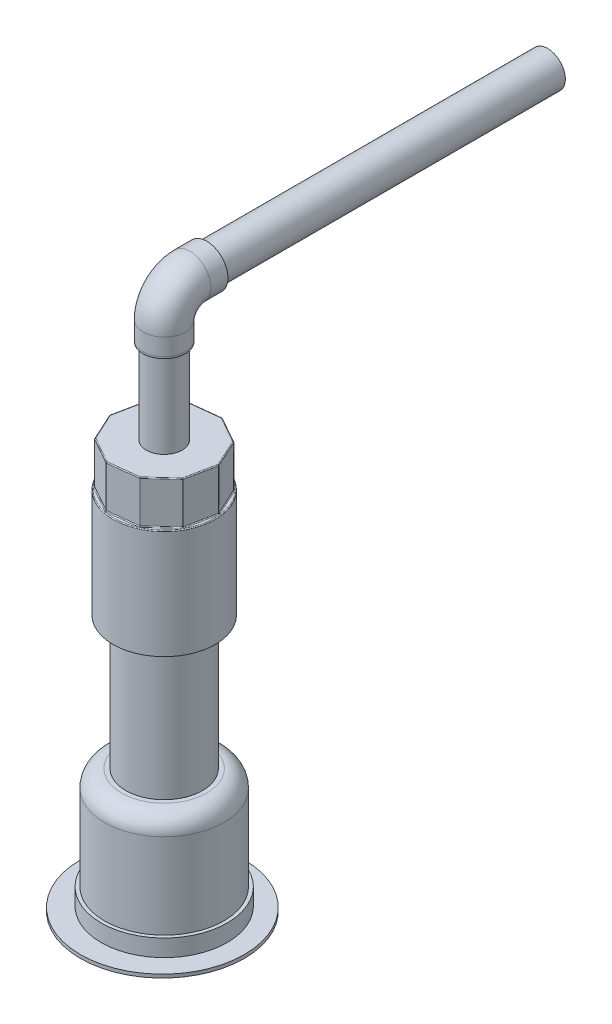
SolidWorks part; units mm, degrees
ref_plane "Front Plane" through (0, 0, 0) normal (0, 0, 1) x (1, 0, 0)
ref_plane "Top Plane" through (0, 0, 0) normal (0, 1, 0) x (1, 0, 0)
ref_plane "Right Plane" through (0, 0, 0) normal (1, 0, 0) x (0, 0, -1)
sketch "Sketch3" plane through (0, 0, 0) normal (0, 1, 0) x (1, 0, 0)
  circle A0 centre (0, -1.0667) radius 48.1
  dimension "D1" = 96.2
extrude "Boss-Extrude3" add sketch "Sketch3" along normal blind 200 contours A0
sketch "Sketch4" plane through (0, 200, 0) normal (0, 1, 0) x (1, 0, 0)
  circle A0 centre (0, 0) radius 35
  circle M2 centre (0, -1.0667) radius 48.1
  dimension "D1" = 70
extrude "Cut-Extrude2" cut sketch "Sketch4" against normal blind 198 contours A0 M2 region at (-46.7395, 200, 1.0667)
sketch "Sketch5" plane through (0, 200, 0) normal (0, 1, 0) x (1, 0, 0)
  circle A0 centre (0, 0) radius 22.5
  circle M2 centre (0, 0) radius 35
  dimension "D1" = 45
extrude "Cut-Extrude3" cut sketch "Sketch5" against normal blind 128 contours A0 M2 region at (-34.0101, 200, 0)
fillet "Fillet1" radius 10 1 edges at (0, 72, 35) type face fillet first side face at (0, 72, 22.5) second side face at (0, 2, 35)
ref_plane "Plane2" through (0, 150, 0) normal (0, 1, 0) x (1, 0, 0)
sketch "Sketch6" plane through (0, 200, 0) normal (0, 1, 0) x (1, 0, 0)
  circle A0 centre (0, 0) radius 20.5
  circle A1 centre (0, 0) radius 22.5 construction
  dimension "D1" = 2
extrude "Cut-Extrude4" cut sketch "Sketch6" against normal up to vertex (200 mm away) up to point (0, 0, 0)
fillet "Fillet2" radius 2 1 edges at (0, 2, 35) type face fillet first side face at (0, 2, 35) second side face at (0, 62, 35)
sketch "Sketch7" plane through (0, 0, 0) normal (0, -1, 0) x (-1, 0, 0)
  circle A0 centre (0, 0) radius 34.5
  dimension "D1" = 69
extrude "Cut-Extrude9" cut sketch "Sketch7" against normal blind 56
fillet "Fillet3" radius 4 1 edges at (0, 56, -34.5) type face fillet first side face at (0, 56, -34.5) second side face at (0, 56, -34.5)
sketch "Sketch8" plane through (0, 56, 0) normal (0, -1, 0) x (1, 0, 0)
  line L0 (-12.8244, 15.9933) -> (-10.2294, 12.757)
  line L1 (2.2407, 20.3772) -> (1.7873, 16.2539)
  line L2 (15.9933, 12.8244) -> (12.757, 10.2294)
  line L3 (20.3772, -2.2407) -> (16.2539, -1.7873)
  line L4 (12.8244, -15.9933) -> (10.2294, -12.757)
  line L5 (-2.2407, -20.3772) -> (-1.7873, -16.2539)
  line L6 (-15.9933, -12.8244) -> (-12.757, -10.2294)
  line L7 (-20.3772, 2.2407) -> (-16.2539, 1.7873)
  line L8 (-14.3847, 14.7421) -> (-11.7897, 11.5059)
  line L9 (-20.5958, 0.2527) -> (-16.4725, -0.2007)
  line L10 (-14.7421, -14.3847) -> (-11.5059, -11.7897)
  line L11 (-0.2527, -20.5958) -> (0.2007, -16.4725)
  line L12 (14.3847, -14.7421) -> (11.7897, -11.5059)
  line L13 (20.5958, -0.2527) -> (16.4725, 0.2007)
  line L14 (14.7421, 14.3847) -> (11.5059, 11.7897)
  line L15 (0.2527, 20.5958) -> (-0.2007, 16.4725)
  line L16 (1.4401, 6.4909) -> (3.1298, 7.561)
  line L17 (-3.1333, 7.5595) -> (-3.5715, 5.6081)
  line L18 (-7.561, 3.1298) -> (-6.4909, 1.4401)
  line L19 (7.5595, 3.1333) -> (5.6081, 3.5715)
  line L20 (6.4909, -1.4401) -> (7.561, -3.1298)
  line L21 (3.5715, -5.6081) -> (3.1333, -7.5595)
  line L22 (-1.4401, -6.4909) -> (-3.1298, -7.561)
  line L23 (-5.6081, -3.5715) -> (-7.5595, -3.1333)
  line L24 (2.2407, 20.3772) -> (0.2527, 20.5958)
  line L25 (14.7421, 14.3847) -> (15.9933, 12.8244)
  line L26 (20.5958, -0.2527) -> (20.3772, -2.2407)
  line L27 (14.3847, -14.7421) -> (12.8244, -15.9933)
  line L28 (-0.2527, -20.5958) -> (-2.2407, -20.3772)
  line L29 (-14.7421, -14.3847) -> (-15.9933, -12.8244)
  line L30 (-20.5958, 0.2527) -> (-20.3772, 2.2407)
  line L31 (-12.8244, 15.9933) -> (-14.3847, 14.7421)
  circle A0 centre (0, 0) radius 8.1831
  circle A1 centre (0, 0) radius 10.8912
  circle A2 centre (0, 0) radius 13.5226
  circle A3 centre (0, 0) radius 16.3519
  circle A4 centre (0, 0) radius 20.5
  arc A5 (-10.2294, 12.757) -> (-9.222, 9.8903) centre (-13.8046, 9.8903) cw
  arc A6 (-9.222, 9.8903) -> (-7.3599, 8.0282) centre (-7.3599, 9.8903) ccw
  arc A7 (-7.3599, 8.0282) -> (-3.1333, 7.5595) centre (-7.3599, -11.2637) cw
  arc A8 (0.4725, 10.881) -> (3.1298, 7.561) centre (-13.1689, -2.7605) cw
  arc A9 (0.4725, 13.5144) -> (0.4725, 10.881) centre (1.7893, 12.1977) ccw
  arc A10 (1.7873, 16.2539) -> (0.4725, 13.5144) centre (-2.7678, 16.7548) cw
  arc A11 (8.0282, 7.3599) -> (7.5595, 3.1333) centre (-11.2637, 7.3599) cw
  arc A12 (9.8903, 9.222) -> (8.0282, 7.3599) centre (9.8903, 7.3599) ccw
  arc A13 (12.757, 10.2294) -> (9.8903, 9.222) centre (9.8903, 13.8046) cw
  arc A14 (10.881, -0.4725) -> (7.561, -3.1298) centre (-2.7605, 13.1689) cw
  arc A15 (13.5144, -0.4725) -> (10.881, -0.4725) centre (12.1977, -1.7893) ccw
  arc A16 (16.2539, -1.7873) -> (13.5144, -0.4725) centre (16.7548, 2.7678) cw
  arc A17 (7.3599, -8.0282) -> (3.1333, -7.5595) centre (7.3599, 11.2637) cw
  arc A18 (9.222, -9.8903) -> (7.3599, -8.0282) centre (7.3599, -9.8903) ccw
  arc A19 (10.2294, -12.757) -> (9.222, -9.8903) centre (13.8046, -9.8903) cw
  arc A20 (-0.4725, -10.881) -> (-3.1298, -7.561) centre (13.1689, 2.7605) cw
  arc A21 (-0.4725, -13.5144) -> (-0.4725, -10.881) centre (-1.7893, -12.1977) ccw
  arc A22 (-1.7873, -16.2539) -> (-0.4725, -13.5144) centre (2.7678, -16.7548) cw
  arc A23 (-8.0282, -7.3599) -> (-7.5595, -3.1333) centre (11.2637, -7.3599) cw
  arc A24 (-9.8903, -9.222) -> (-8.0282, -7.3599) centre (-9.8903, -7.3599) ccw
  arc A25 (-12.757, -10.2294) -> (-9.8903, -9.222) centre (-9.8903, -13.8046) cw
  arc A26 (-10.881, 0.4725) -> (-7.561, 3.1298) centre (2.7605, -13.1689) cw
  arc A27 (-13.5144, 0.4725) -> (-10.881, 0.4725) centre (-12.1977, 1.7893) ccw
  arc A28 (-16.2539, 1.7873) -> (-13.5144, 0.4725) centre (-16.7548, -2.7678) cw
  arc A29 (-11.7897, 11.5059) -> (-11.222, 9.8903) centre (-13.8046, 9.8903) cw
  arc A30 (-11.222, 9.8903) -> (-7.3599, 6.0282) centre (-7.3599, 9.8903) ccw
  arc A31 (-7.3599, 6.0282) -> (-3.5715, 5.6081) centre (-7.3599, -11.2637) cw
  arc A32 (-16.4725, -0.2007) -> (-14.9286, -0.9417) centre (-16.7548, -2.7678) cw
  arc A33 (-14.9286, -0.9417) -> (-9.4668, -0.9417) centre (-12.1977, 1.7893) ccw
  arc A34 (-9.4668, -0.9417) -> (-6.4909, 1.4401) centre (2.7605, -13.1689) cw
  arc A35 (-11.5059, -11.7897) -> (-9.8903, -11.222) centre (-9.8903, -13.8046) cw
  arc A36 (-9.8903, -11.222) -> (-6.0282, -7.3599) centre (-9.8903, -7.3599) ccw
  arc A37 (-6.0282, -7.3599) -> (-5.6081, -3.5715) centre (11.2637, -7.3599) cw
  arc A38 (0.2007, -16.4725) -> (0.9417, -14.9286) centre (2.7678, -16.7548) cw
  arc A39 (0.9417, -14.9286) -> (0.9417, -9.4668) centre (-1.7893, -12.1977) ccw
  arc A40 (0.9417, -9.4668) -> (-1.4401, -6.4909) centre (13.1689, 2.7605) cw
  arc A41 (11.7897, -11.5059) -> (11.222, -9.8903) centre (13.8046, -9.8903) cw
  arc A42 (11.222, -9.8903) -> (7.3599, -6.0282) centre (7.3599, -9.8903) ccw
  arc A43 (7.3599, -6.0282) -> (3.5715, -5.6081) centre (7.3599, 11.2637) cw
  arc A44 (16.4725, 0.2007) -> (14.9286, 0.9417) centre (16.7548, 2.7678) cw
  arc A45 (14.9286, 0.9417) -> (9.4668, 0.9417) centre (12.1977, -1.7893) ccw
  arc A46 (9.4668, 0.9417) -> (6.4909, -1.4401) centre (-2.7605, 13.1689) cw
  arc A47 (11.5059, 11.7897) -> (9.8903, 11.222) centre (9.8903, 13.8046) cw
  arc A48 (9.8903, 11.222) -> (6.0282, 7.3599) centre (9.8903, 7.3599) ccw
  arc A49 (6.0282, 7.3599) -> (5.6081, 3.5715) centre (-11.2637, 7.3599) cw
  arc A50 (-0.2007, 16.4725) -> (-0.9417, 14.9286) centre (-2.7678, 16.7548) cw
  arc A51 (-0.9417, 14.9286) -> (-0.9417, 9.4668) centre (1.7893, 12.1977) ccw
  arc A52 (-0.9417, 9.4668) -> (1.4401, 6.4909) centre (-13.1689, -2.7605) cw
  point P135 (0, 0)
  dimension "D2" = 2
  dimension "D1" = 8
extrude "Boss-Extrude15" add sketch "Sketch8" against normal blind 3 contours A52 A0 L17 A31 L18 A34 L23 A37 L22 A40 L21 A43 L20 A46 L19 A49 L16 | L5 A22 A21 A20 L22 A40 A39 A38 L11 L28 | L4 A19 A18 A17 L21 A43 A42 A41 L12 L27 | A15 A14 L20 A46 A45 A44 L13 L26 L3 A16 | A48 A49 L19 A11 A12 A13 L2 L25 L14 A47 | A52 L16 A8 A9 A10 L1 L24 L15 A50 A51 | A30 A31 L17 A7 A6 A5 L0 L31 L8 A29 | L9 A32 A33 A34 L18 A26 A27 A28 L7 L30 | L6 A25 A24 A23 L23 A37 A36 A35 L10 L29 region at (0, 56, 0)
sketch "Sketch9" plane through (0, 56, 0) normal (0, -1, 0) x (1, 0, 0)
  circle A0 centre (0, 0) radius 16.6577
  circle A1 centre (0, 0) radius 13.5859
extrude "Boss-Extrude16" add sketch "Sketch9" against normal blind 3
sketch "Sketch10" plane through (0, 150, 0) normal (0, 1, 0) x (1, 0, 0)
  circle A0 centre (0, 0) radius 30
  circle A1 centre (0, 0) radius 25 construction
  dimension "D1" = 5
extrude "Boss-Extrude17" add sketch "Sketch10" along normal blind 89
sketch "Sketch11" plane through (0, 239, 0) normal (0, 1, 0) x (1, 0, 0)
  circle A0 centre (0, 0) radius 10.5
  dimension "D1" = 21
extrude "Cut-Extrude10" cut sketch "Sketch11" against normal blind 89
sketch "Sketch12" plane through (0, 239, 0) normal (0, 1, 0) x (1, 0, 0)
  circle A0 centre (0, 0) radius 23
  circle A1 centre (0, 0) radius 30 construction
  circle M3 centre (0, 0) radius 30
  dimension "D1" = 7
extrude "Cut-Extrude12" cut sketch "Sketch12" against normal blind 25 contours A0 M3 region at (-29.1515, 239, 0)
sketch "Sketch13" plane through (0, 239, 0) normal (0, 1, 0) x (1, 0, 0)
  line L1 (21.2917, 19.564) -> (5.7259, 28.3426)
  line L2 (5.7259, 28.3426) -> (-12.027, 26.2953)
  line L3 (-12.027, 26.2953) -> (-25.186, 14.204)
  line L4 (-25.186, 14.204) -> (-28.7248, -3.3127)
  line L5 (-28.7248, -3.3127) -> (-21.2917, -19.564)
  line L6 (-21.2917, -19.564) -> (-5.7259, -28.3426)
  line L7 (-5.7259, -28.3426) -> (12.027, -26.2953)
  line L8 (12.027, -26.2953) -> (25.186, -14.204)
  line L9 (25.186, -14.204) -> (28.7248, 3.3127)
  line L10 (28.7248, 3.3127) -> (21.2917, 19.564)
  circle A0 centre (0, 0) radius 27.5 construction
  circle A2 centre (0, 0) radius 23 construction
  circle M11 centre (0, 0) radius 10.5
  circle M12 centre (0, 0) radius 23
  dimension "D1" = 27.5
extrude "Boss-Extrude18" add sketch "Sketch13" against normal up to surface (25 mm away) contours M12 M11 | L1 L2 L3 L4 L5 L6 L7 L8 L9 L10 region at (-22.3495, 239, 0) up to face at (0, 214, 23)
fillet "Fillet4" radius 0.5 31 edges at (0, 214, 30) (-13.5088, 239, 23.9533) (-13.5088, 214, 23.9533) (-25.0083, 239, 11.4384) (-21.2917, 226.5, 19.564) (-25.0083, 214, 11.4384) (-26.9554, 239, -5.4457) (-28.7248, 226.5, 3.3127) (-26.9554, 214, -5.4457) (-18.6065, 239, -20.2496) (-25.186, 226.5, -14.204) (-18.6065, 214, -20.2496) (-3.1505, 239, -27.3189) (-12.027, 226.5, -26.2953) (-3.1505, 214, -27.3189) (13.5088, 239, -23.9533) (5.7259, 226.5, -28.3426) (13.5088, 214, -23.9533) (25.0083, 239, -11.4384) (21.2917, 226.5, -19.564) (25.0083, 214, -11.4384) (26.9554, 239, 5.4457) (28.7248, 226.5, -3.3127) (26.9554, 214, 5.4457) (-5.7259, 226.5, 28.3426) (3.1505, 239, 27.3189) (3.1505, 214, 27.3189) (12.027, 226.5, 26.2953) (18.6065, 239, 20.2496) (25.186, 226.5, 14.204) (18.6065, 214, 20.2496)
sketch "Sketch14" plane through (0, 239, 0) normal (0, 1, 0) x (1, 0, 0)
  circle A0 centre (0, 0) radius 10.5
extrude "Boss-Extrude19" add sketch "Sketch14" along normal blind 50 separate body
sketch "Sketch15" plane through (0, 289, 0) normal (0, 1, 0) x (1, 0, 0)
  circle A0 centre (0, 0) radius 9.5
  circle A1 centre (0, 0) radius 10.5 construction
  dimension "D1" = 1
extrude "Cut-Extrude13" cut sketch "Sketch15" against normal blind 178
sketch "Sketch89" plane through (0, 289, 0) normal (0, 1, 0) x (1, 0, 0)
  circle A0 centre (0, 0) radius 12.4166
  circle A1 centre (0, 0) radius 10.5 construction
  circle A2 centre (0, 0) radius 10.5
  dimension "D1" = 1.9166
extrude "Boss-Extrude20" add sketch "Sketch89" along normal blind 1 separate body
sketch "Sketch91" plane through (0, 0, 0) normal (1, 0, 0) x (0, 0, -1)
  line L0 (0, 290) -> (0, 300)
  line L1 (12.4166, 290) -> (-12.4166, 290) construction
  line L2 (15, 315) -> (25, 315)
  arc A0 (0, 300) -> (15, 315) centre (15, 300) cw
  dimension "D1" = 15
  dimension "D2" = 10
  dimension "D3" = 10
sweep "Sweep2" add path "Sketch91" circular profile diameter 24.83 parameters "D3"=24.83
shell "Shell3" thickness 2 removed face at (12.415, 315, -25)
sketch "Sketch138" plane through (0, 0, -25) normal (0, 0, -1) x (-1, 0, 0)
  circle A0 centre (0, 315) radius 10.415
  circle A1 centre (0, 315) radius 10.415 construction
  dimension "D1" = 0
  dimension "D2" = 20.83
extrude "Boss-Extrude21" add sketch "Sketch138" along normal blind 200 separate body
shell "Shell4" thickness 1 removed face at (-10.415, 315, -225)
sketch "Sketch139" plane through (0, 2, 0) normal (0, 1, 0) x (1, 0, 0)
  circle A0 centre (0, 0) radius 37
  circle A1 centre (0, 0) radius 37 construction
  circle A2 centre (0, 0) radius 35
  circle A3 centre (0, 0) radius 35 construction
  circle M1 centre (0, 0) radius 37
  dimension "D1" = 0
  dimension "D2" = 0
extrude "Boss-Extrude22" add sketch "Sketch139" along normal blind 10 contours A2 M1 region at (-35.9535, 2, 0)
sketch "Sketch140" plane through (0, 12, 0) normal (0, 1, 0) x (1, 0, 0)
  circle A0 centre (0, 0) radius 34.5
  circle A1 centre (0, 0) radius 34.5 construction
  circle A2 centre (0, 0) radius 33.5
  dimension "D1" = 0
  dimension "D2" = 1
extrude "Boss-Extrude23" add sketch "Sketch140" against normal blind 12 contours A0 | A2
